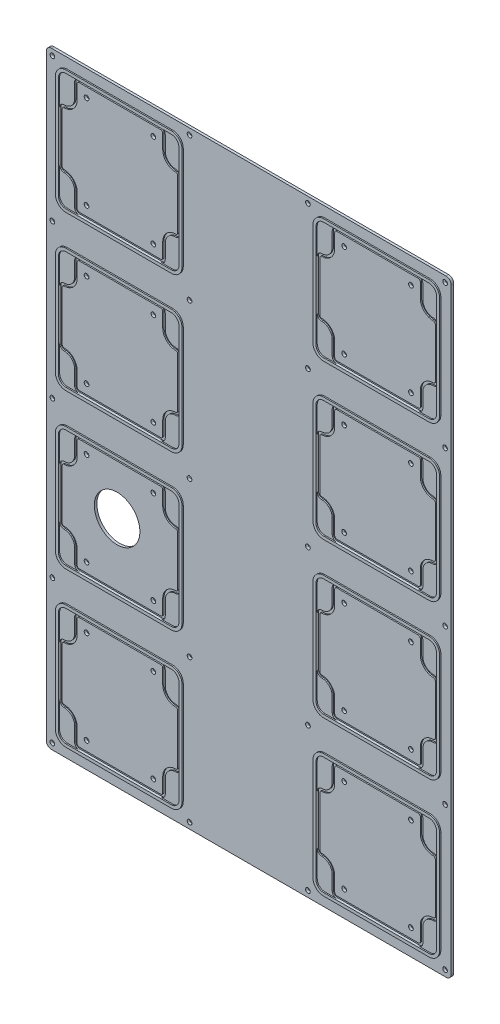
SolidWorks part; units mm, degrees
ref_plane "Front Plane" through (0, 0, 0) normal (0, 0, 1) x (1, 0, 0)
ref_plane "Top Plane" through (0, 0, 0) normal (0, 1, 0) x (1, 0, 0)
ref_plane "Right Plane" through (0, 0, 0) normal (1, 0, 0) x (0, 0, -1)
sketch "Sketch1" plane through (0, 0, 0) normal (0, 0, 1) x (1, 0, 0)
  line L1 (0, 0) -> (254, 0)
  line L2 (0, 0) -> (0, 381)
  line L3 (0, 381) -> (254, 381)
  line L4 (254, 0) -> (254, 381)
  dimension "D1" = 381
  dimension "D2" = 254
extrude "Boss-Extrude1" add sketch "Sketch1" along normal blind 1.5875
sketch "Sketch2" plane through (0, 0, 1.5875) normal (0, 0, 1) x (1, 0, 0)
  line L0 (89.8652, 377.19) -> (89.8652, 3.81) construction
  line L1 (0, 381) -> (254, 381) construction
  line L2 (127, 381) -> (127, 377.19) construction
  line L3 (3.81, 377.19) -> (250.19, 377.19) construction
  line L5 (164.1348, 377.19) -> (164.1348, 3.81) construction
  line L6 (3.81, 377.19) -> (3.81, 3.81) construction
  line L7 (3.81, 3.81) -> (250.19, 3.81) construction
  line L8 (250.19, 3.81) -> (250.19, 377.19) construction
  line L9 (3.81, 190.5) -> (250.19, 190.5) construction
  line L10 (3.81, 287.3756) -> (250.19, 287.3756) construction
  line L11 (3.81, 93.6244) -> (250.19, 93.6244) construction
  line L12 (0, 381) -> (0, 0) construction
  line L13 (0, 190.5) -> (3.81, 190.5) construction
  circle A0 centre (3.81, 377.19) radius 1.4732
  circle A1 centre (89.8652, 377.19) radius 1.4732
  circle A2 centre (164.1348, 377.19) radius 1.4732
  circle A3 centre (250.19, 377.19) radius 1.4732
  circle A4 centre (164.1348, 287.3755) radius 1.4732
  circle A5 centre (3.81, 287.3756) radius 1.4732
  circle A6 centre (250.19, 287.3756) radius 1.4732
  circle A7 centre (89.8652, 287.3756) radius 1.4732
  circle A8 centre (164.1348, 190.5) radius 1.4732
  circle A9 centre (3.81, 191.135) radius 1.4732
  circle A10 centre (250.19, 190.5) radius 1.4732
  circle A11 centre (89.8652, 190.5) radius 1.4732
  circle A12 centre (164.1348, 93.6244) radius 1.4732
  circle A13 centre (3.81, 93.6244) radius 1.4732
  circle A14 centre (250.19, 93.6244) radius 1.4732
  circle A15 centre (89.8652, 93.6244) radius 1.4732
  circle A16 centre (164.1348, 3.81) radius 1.4732
  circle A17 centre (3.81, 3.81) radius 1.4732
  circle A18 centre (250.19, 3.81) radius 1.4732
  circle A19 centre (89.8652, 3.81) radius 1.4732
  dimension "D6" = 2.9464
  dimension "D23" = 0
  dimension "D24" = 0
  dimension "D25" = 0
  dimension "D28" = 0
  dimension "D29" = 0
  dimension "D30" = 0
  dimension "D31" = 0
  dimension "D32" = 86.0552
  dimension "D1" = 246.38
  dimension "D3" = 373.38
  dimension "D4" = 96.8756
  dimension "D5" = 96.8756
  dimension "D7" = 86.0552
  dimension "D8" = 86.0552
  dimension "D9" = 0
  dimension "D10" = 0
  dimension "D11" = 0
  dimension "D12" = 86.0552
  dimension "D13" = 0
  dimension "D14" = 0
  dimension "D15" = 0
  dimension "D16" = 0
  dimension "D17" = 0
  dimension "D18" = 0
  dimension "D19" = 0
  dimension "D20" = 0
  dimension "D21" = 0
  dimension "D22" = 0
  dimension "D26" = 0
  dimension "D27" = 0
extrude "Cut-Extrude1" cut sketch "Sketch2" against normal through all
fillet "Fillet1" radius 3.175 4 edges at (254, 0, 0.7937) (0, 0, 0.7937) (254, 381, 0.7937) (0, 381, 0.7937)
sketch "Sketch3" plane through (0, 0, 1.5875) normal (0, 0, 1) x (1, 0, 0)
  line L0 (9.9695, 45.1866) -> (46.2026, 45.1866) construction
  line L1 (46.2026, 45.1866) -> (46.2026, 9.9695) construction
  line L2 (81.2038, 28.3591) -> (82.4357, 28.3591) construction
  line L3 (82.4357, 29.591) -> (82.4357, 60.7822)
  line L4 (73.0377, 11.2014) -> (73.0377, 20.193)
  line L5 (81.2038, 62.0141) -> (82.4357, 62.0141) construction
  line L6 (71.8058, 9.9695) -> (20.5994, 9.9695)
  line L7 (19.3675, 11.2014) -> (19.3675, 20.193)
  line L8 (11.2014, 28.3591) -> (9.9695, 28.3591) construction
  line L9 (9.9695, 29.591) -> (9.9695, 60.7822)
  line L10 (73.0377, 79.1718) -> (73.0377, 70.1802)
  line L11 (71.8058, 80.4037) -> (20.5994, 80.4037)
  line L12 (3.175, 0) -> (250.825, 0) construction
  line L13 (0, 377.825) -> (0, 3.175) construction
  line L14 (11.2014, 62.0141) -> (9.9695, 62.0141) construction
  line L15 (19.3675, 79.1718) -> (19.3675, 70.1802)
  line L16 (17.78, 79.1718) -> (17.78, 70.1802)
  line L17 (8.382, 29.591) -> (8.382, 60.7822)
  line L18 (17.78, 11.2014) -> (17.78, 20.193)
  line L19 (71.8058, 8.382) -> (20.5994, 8.382)
  line L20 (74.6252, 11.2014) -> (74.6252, 20.193)
  line L21 (84.0232, 29.591) -> (84.0232, 60.7822)
  line L22 (74.6252, 79.1718) -> (74.6252, 70.1802)
  line L23 (71.8058, 81.9912) -> (20.5994, 81.9912)
  arc A0 (19.3675, 20.193) -> (11.2014, 28.3591) centre (11.2014, 20.193) ccw
  arc A1 (9.9695, 29.591) -> (11.2014, 28.3591) centre (11.2014, 29.591) ccw
  arc A2 (19.3675, 11.2014) -> (20.5994, 9.9695) centre (20.5994, 11.2014) ccw
  arc A3 (73.0377, 11.2014) -> (71.8058, 9.9695) centre (71.8058, 11.2014) cw
  arc A4 (82.4357, 29.591) -> (81.2038, 28.3591) centre (81.2038, 29.591) cw
  arc A5 (73.0377, 20.193) -> (81.2038, 28.3591) centre (81.2038, 20.193) cw
  arc A6 (73.0377, 70.1802) -> (81.2038, 62.0141) centre (81.2038, 70.1802) ccw
  arc A7 (82.4357, 60.7822) -> (81.2038, 62.0141) centre (81.2038, 60.7822) ccw
  arc A8 (73.0377, 79.1718) -> (71.8058, 80.4037) centre (71.8058, 79.1718) ccw
  arc A9 (19.3675, 79.1718) -> (20.5994, 80.4037) centre (20.5994, 79.1718) cw
  arc A10 (9.9695, 60.7822) -> (11.2014, 62.0141) centre (11.2014, 60.7822) cw
  arc A11 (19.3675, 70.1802) -> (11.2014, 62.0141) centre (11.2014, 70.1802) cw
  arc A12 (17.78, 70.1802) -> (11.2014, 63.6016) centre (11.2014, 70.1802) cw
  arc A13 (8.382, 60.7822) -> (11.2014, 63.6016) centre (11.2014, 60.7822) cw
  arc A14 (8.382, 29.591) -> (11.2014, 26.7716) centre (11.2014, 29.591) ccw
  arc A15 (17.78, 20.193) -> (11.2014, 26.7716) centre (11.2014, 20.193) ccw
  arc A16 (17.78, 11.2014) -> (20.5994, 8.382) centre (20.5994, 11.2014) ccw
  arc A17 (74.6252, 11.2014) -> (71.8058, 8.382) centre (71.8058, 11.2014) cw
  arc A18 (74.6252, 20.193) -> (81.2038, 26.7716) centre (81.2038, 20.193) cw
  arc A19 (84.0232, 29.591) -> (81.2038, 26.7716) centre (81.2038, 29.591) cw
  arc A20 (84.0232, 60.7822) -> (81.2038, 63.6016) centre (81.2038, 60.7822) ccw
  arc A21 (74.6252, 70.1802) -> (81.2038, 63.6016) centre (81.2038, 70.1802) ccw
  arc A22 (74.6252, 79.1718) -> (71.8058, 81.9912) centre (71.8058, 79.1718) ccw
  arc A23 (17.78, 79.1718) -> (20.5994, 81.9912) centre (20.5994, 79.1718) cw
  point P35 (82.4357, 45.1866)
  dimension "D6" = 8.1661
  dimension "D7" = 2.4638
  dimension "D8" = 1.2319
  dimension "D1" = 9.9695
  dimension "D2" = 9.9695
  dimension "D3" = 19.3675
  dimension "D4" = 28.3591
  dimension "D5" = 45.1866
  dimension "D10" = 46.2026
  dimension "D9" = 1.5875
extrude "Cut-Extrude2" cut sketch "Sketch3" against normal blind 0.7937
sketch "Sketch4" plane through (0, 0, 1.5875) normal (0, 0, 1) x (1, 0, 0)
  line L0 (8.382, 60.7822) -> (8.382, 77.2287)
  line L1 (13.1445, 81.9912) -> (20.5994, 81.9912)
  line L2 (20.5994, 81.9912) -> (79.2607, 81.9912)
  line L3 (84.0232, 77.2287) -> (84.0232, 13.1445)
  line L4 (79.2607, 8.382) -> (13.1445, 8.382)
  line L5 (8.382, 13.1445) -> (8.382, 60.7822)
  line L6 (6.477, 60.7822) -> (6.477, 77.2287)
  line L7 (13.1445, 83.8962) -> (20.5994, 83.8962)
  line L8 (20.5994, 83.8962) -> (79.2607, 83.8962)
  line L9 (85.9282, 77.2287) -> (85.9282, 13.1445)
  line L10 (79.2607, 6.477) -> (13.1445, 6.477)
  line L11 (6.477, 13.1445) -> (6.477, 60.7822)
  arc A0 (13.1445, 81.9912) -> (8.382, 77.2287) centre (13.1445, 77.2287) ccw
  arc A1 (79.2607, 81.9912) -> (84.0232, 77.2287) centre (79.2607, 77.2287) cw
  arc A2 (84.0232, 13.1445) -> (79.2607, 8.382) centre (79.2607, 13.1445) cw
  arc A3 (8.382, 13.1445) -> (13.1445, 8.382) centre (13.1445, 13.1445) ccw
  arc A4 (13.1445, 83.8962) -> (6.477, 77.2287) centre (13.1445, 77.2287) ccw
  arc A5 (79.2607, 83.8962) -> (85.9282, 77.2287) centre (79.2607, 77.2287) cw
  arc A6 (85.9282, 13.1445) -> (79.2607, 6.477) centre (79.2607, 13.1445) cw
  arc A7 (6.477, 13.1445) -> (13.1445, 6.477) centre (13.1445, 13.1445) ccw
  dimension "D1" = 4.7625
  dimension "D2" = 1.905
extrude "Boss-Extrude2" add sketch "Sketch4" along normal blind 0.7937
sketch "Sketch5" plane through (0, 0, 1.5875) normal (0, 0, 1) x (1, 0, 0)
  line L0 (9.9695, 45.1866) -> (82.4357, 45.1866) construction
  line L1 (9.9695, 60.7822) -> (9.9695, 29.591) construction
  line L2 (82.4357, 29.591) -> (82.4357, 60.7822) construction
  line L3 (82.4357, 45.1866) -> (46.2026, 45.1866) construction
  line L4 (46.2026, 45.1866) -> (46.2026, 80.4037) construction
  line L5 (71.8058, 80.4037) -> (20.5994, 80.4037) construction
  circle A0 centre (25.2476, 74.3966) radius 1.4732
  circle A1 centre (67.1576, 74.3966) radius 1.4732
  circle A2 centre (67.1576, 15.9766) radius 1.4732
  circle A3 centre (25.2476, 15.9766) radius 1.4732
  dimension "D1" = 2.9464
  dimension "D2" = 20.955
  dimension "D3" = 29.21
extrude "Cut-Extrude3" cut sketch "Sketch5" against normal through all
pattern_linear "LPattern1" count 4 spacing 96.8756 along (0, 1, 0) count 2 spacing 161.5948 along (1, 0, 0) of "Cut-Extrude2", "Boss-Extrude2", "Cut-Extrude3"
sketch "Sketch6" plane through (0, 0, 1.5875) normal (0, 0, 1) x (1, 0, 0)
  circle A0 centre (44.4246, 146.0754) radius 14.2875
  dimension "D1" = 28.575
extrude "Cut-Extrude4" cut sketch "Sketch6" against normal blind 2.54
